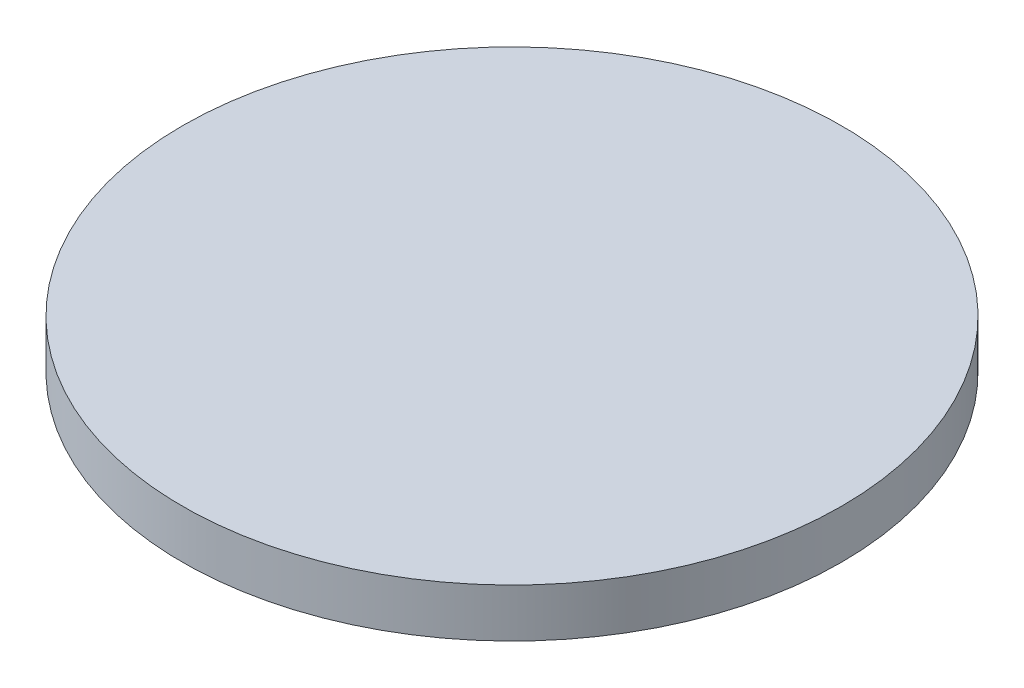
SolidWorks part; units mm, degrees
material "Glass"
ref_plane "Front Plane" through (0, 0, 0) normal (0, 0, 1) x (1, 0, 0)
ref_plane "Top Plane" through (0, 0, 0) normal (0, 1, 0) x (1, 0, 0)
ref_plane "Right Plane" through (0, 0, 0) normal (1, 0, 0) x (0, 0, -1)
sketch "Sketch1" plane through (0, 0, 0) normal (0, 0, 1) x (1, 0, 0)
  line L0 (-55.2, -0.2) -> (-52.5, -0.2)
  line L1 (0, 0) -> (-55, 0)
  line L2 (0, 0) -> (0, 8.1)
  line L3 (0, 8.1) -> (-55, 8.1)
  line L4 (-55, 0) -> (-55, 8.1)
  line L5 (-52.5, -0.2) -> (-52.5, -3.2)
  line L6 (-52.5, -3.2) -> (-65.2, -3.2)
  line L7 (-65.2, -3.2) -> (-65.2, 11.8)
  line L12 (-55.2, 11.8) -> (-55.2, -0.2)
  line L13 (-55.2, 11.8) -> (-65.2, 11.8)
  line L14 (0, 0) -> (0, 30.013) construction
sketch "Sketch3" plane through (0, 0, 0) normal (0, 0, 1) x (1, 0, 0)
  line L0 (0, 0) -> (0, 30.013) construction
  line L1 (0, 0) -> (0, 8.1) construction
  line L2 (0, 0) -> (-55, 0) construction
  line L3 (-55, 0) -> (-55, 8.1) construction
  line L4 (0, 8.1) -> (-55, 8.1) construction
  line L5 (0, 0) -> (0, 30.013) construction
  line L6 (0, 0) -> (0, 8.1)
  line L7 (0, 0) -> (-55, 0)
  line L8 (-55, 0) -> (-55, 8.1)
  line L9 (0, 8.1) -> (-55, 8.1)
revolve "Filter" add sketch "Sketch3" angle 360 about L5 region at (-27.5, 4.05, 0)
